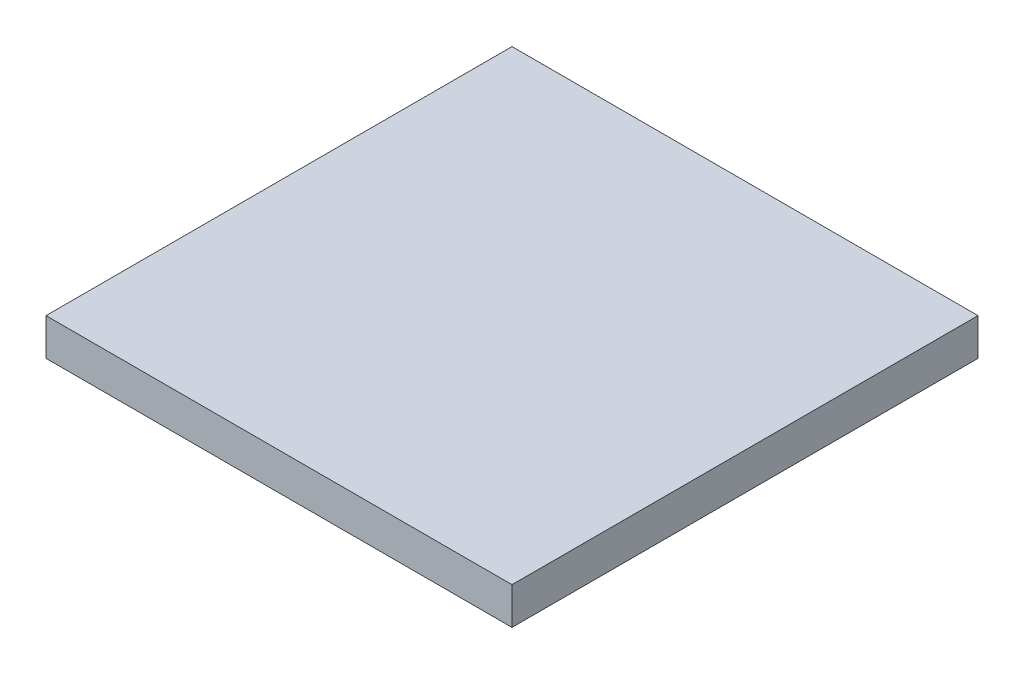
SolidWorks part; units mm, degrees
ref_plane "Front Plane" through (0, 0, 0) normal (0, 0, 1) x (1, 0, 0)
ref_plane "Top Plane" through (0, 0, 0) normal (0, 1, 0) x (1, 0, 0)
ref_plane "Right Plane" through (0, 0, 0) normal (1, 0, 0) x (0, 0, -1)
sketch "Sketch1" plane through (0, 0, 0) normal (0, 1, 0) x (1, 0, 0)
  line L1 (-457.2, 457.2) -> (457.2, 457.2)
  line L2 (-457.2, 457.2) -> (-457.2, -457.2)
  line L3 (-457.2, -457.2) -> (457.2, -457.2)
  line L4 (457.2, 457.2) -> (457.2, -457.2)
  line L5 (-457.2, 457.2) -> (457.2, -457.2) construction
  line L6 (-457.2, -457.2) -> (457.2, 457.2) construction
  point P0 (0, 0)
  dimension "D1" = 914.4
  dimension "D2" = 914.4
extrude "Boss-Extrude1" add sketch "Sketch1" along normal blind 72.644
ref_axis "CentralAxis" through (0, 40.005, 0) along (0, -1, 0)
